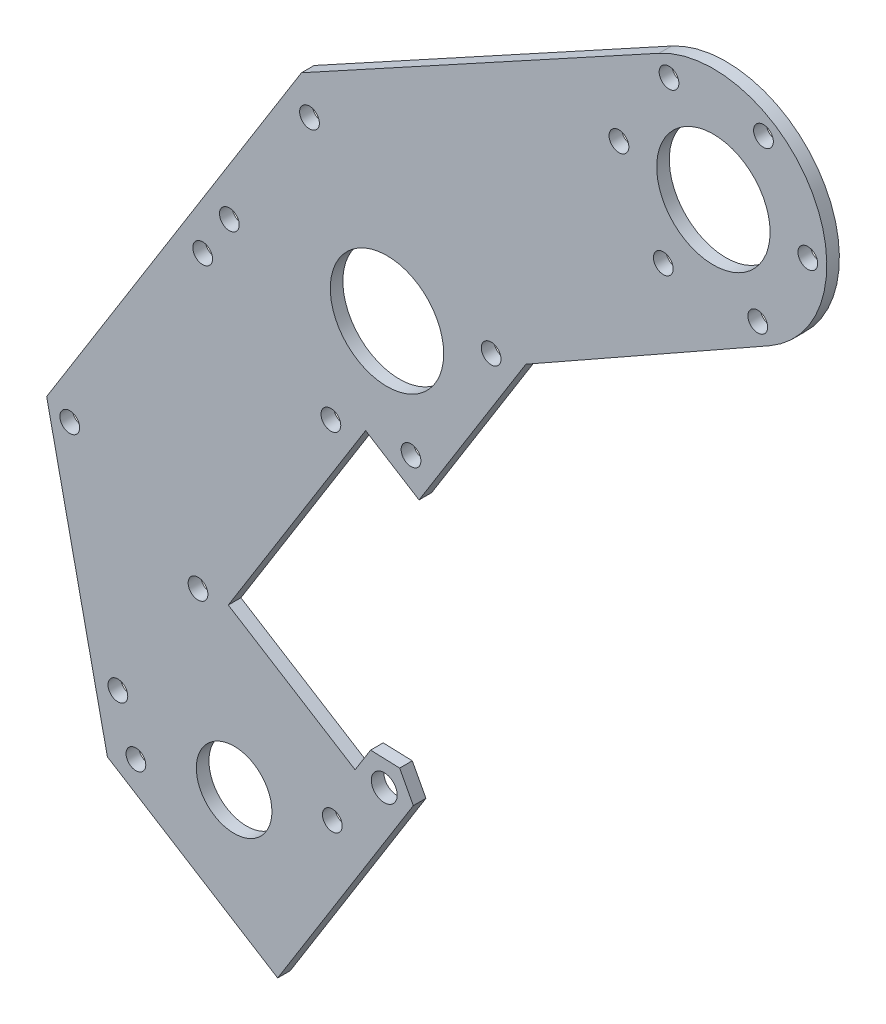
SolidWorks part; units mm, degrees
material "6061 Alloy"
ref_plane "Front Plane" through (0, 0, 0) normal (0, 0, 1) x (1, 0, 0)
ref_plane "Top Plane" through (0, 0, 0) normal (0, 1, 0) x (1, 0, 0)
ref_plane "Right Plane" through (0, 0, 0) normal (1, 0, 0) x (0, 0, -1)
sketch "Sketch1" plane through (0, 0, -14.1946) normal (0, 0, 1) x (1, 0, 0)
  line L0 (-11.4036, 461.0409) -> (18.8813, 509.5069)
  line L1 (-54.3079, 487.8505) -> (-69.6155, 558.824)
  line L2 (8.1111, 516.2368) -> (-23.8465, 536.2061)
  line L3 (18.8813, 509.5069) -> (22.7847, 515.7536)
  line L4 (-11.4036, 461.0409) -> (-54.3079, 487.8505)
  line L5 (-69.6155, 558.824) -> (-5.4017, 661.5875)
  line L6 (-23.8465, 536.2061) -> (10.7592, 591.5868)
  line L9 (12.0145, 522.4836) -> (8.1111, 516.2368)
  line L10 (51.1419, 626.2552) -> (112.462, 660.9373)
  line L11 (10.7592, 591.5868) -> (24.222, 583.1743)
  line L13 (24.222, 583.1743) -> (51.1419, 626.2552)
  line L16 (-5.4017, 661.5875) -> (84.678, 710.8773)
  line L17 (17.3996, 519.1186) -> (21.5031, 525.6857) construction
  line L18 (22.7847, 515.7536) -> (19.3423, 522.2277)
  line L19 (19.3423, 522.2277) -> (12.0145, 522.4836)
  circle A2 centre (16.1415, 618.1747) radius 14.2875
  circle A3 centre (-22.3737, 496.6228) radius 9.525
  circle A5 centre (98.3945, 685.8096) radius 14.2875
  arc A7 (112.462, 660.9373) -> (84.678, 710.8773) centre (98.3945, 685.8096) ccw
  circle A8 centre (16.1415, 618.1747) radius 127.508 construction
  circle A9 centre (15.4568, 516.0095) radius 6.35 construction
  point P12 (-22.3737, 496.6228)
  point P33 (98.3945, 685.8096)
  dimension "D1" = 120
extrude "Boss-Extrude1" add sketch "Sketch1" along normal blind 3.175
sketch "Sketch17" plane through (0, 0, -11.0196) normal (0, 0, 1) x (1, 0, 0)
  line L0 (-47.1227, 490.909) -> (-22.3737, 496.6228)
  line L1 (-22.3737, 496.6228) -> (2.3753, 502.3365)
  line L2 (16.1415, 618.1747) -> (37.6819, 604.7147) construction
  line L12 (24.222, 583.1743) -> (51.1419, 626.2552) construction
  line L13 (37.6819, 604.7147) -> (27.587, 588.5594) construction
  line L14 (27.587, 588.5594) -> (22.2019, 591.9244) construction
  line L15 (22.2019, 591.9244) -> (-28.9566, 623.8918) construction
  line L16 (-5.4017, 661.5875) -> (-69.6155, 558.824) construction
  line L17 (-28.9566, 623.8918) -> (-23.5715, 620.5268) construction
  line L18 (-23.5715, 620.5268) -> (-3.3816, 652.8374) construction
  line L19 (-3.3816, 652.8374) -> (42.3918, 624.2351) construction
  line L20 (10.7592, 591.5868) -> (5.3741, 594.9518) construction
  line L21 (5.3741, 594.9518) -> (-31.4748, 535.9811) construction
  line L22 (-31.4748, 535.9811) -> (-51.6648, 503.6705) construction
  line L23 (5.3741, 594.9518) -> (2.0091, 589.5667) construction
  line L24 (-31.4748, 535.9811) -> (-63.7855, 556.1711) construction
  line L25 (2.0091, 589.5667) -> (-30.3015, 609.7566) construction
  circle A0 centre (-22.3737, 496.6228) radius 25.4
  dimension "D1" = 50.8
hole_wizard "#10 Clearance Hole2" positions "Sketch20" profile "Sketch21" hole size "#10" standard "ANSI Inch" end condition through all
sketch "Sketch20" plane through (0, 0, -11.0196) normal (0, 0, 1) x (1, 0, 0)
  point P0 (2.3753, 502.3365)
  point P3 (-47.1227, 490.909)
  point P24 (-3.3816, 652.8374)
  point P27 (42.3918, 624.2351)
  point P30 (22.2019, 591.9244)
  point P33 (-23.5715, 620.5268)
  point P42 (-31.4748, 535.9811)
  point P45 (-63.7855, 556.1711)
  point P48 (-51.6648, 503.6705)
  point P54 (2.0091, 589.5667)
  point P57 (-30.3015, 609.7566)
sketch "Sketch21" plane through (2.3753, 502.3365, -11.0196) normal (1, 0, 0) x (0, -1, 0)
  line L0 (0, 0) -> (0, 3.175)
  line L1 (0, 3.175) -> (2.4892, 3.175)
  line L2 (2.4892, 3.175) -> (2.4892, 0)
  line L5 (2.4892, 0) -> (0, 0)
  line L11 (0, -6.35) -> (0, 107.95) construction
  dimension "Thru Hole Dia." = 4.9784
  dimension "Thru Hole Depth" = 3.175
sketch "Sketch22" plane through (0, 0, -11.0196) normal (0, 0, 1) x (1, 0, 0)
  line L0 (98.3945, 685.8096) -> (111.0132, 706.0038) construction
  line L2 (111.0132, 706.0038) -> (87.2152, 706.8348) construction
  line L3 (87.2152, 706.8348) -> (74.5965, 686.6407) construction
  line L4 (74.5965, 686.6407) -> (85.7758, 665.6155) construction
  line L5 (85.7758, 665.6155) -> (109.5738, 664.7845) construction
  line L6 (109.5738, 664.7845) -> (122.1925, 684.9786) construction
  line L7 (122.1925, 684.9786) -> (111.0132, 706.0038) construction
  circle A0 centre (98.3945, 685.8096) radius 23.8125 construction
hole_wizard "#10 Clearance Hole3" positions "Sketch23" profile "Sketch24" hole size "#10" standard "ANSI Inch" end condition through all
sketch "Sketch23" plane through (0, 0, -11.0196) normal (0, 0, 1) x (1, 0, 0)
  point P0 (111.0132, 706.0038)
  point P3 (122.1925, 684.9786)
  point P6 (109.5738, 664.7845)
  point P9 (85.7758, 665.6155)
  point P12 (74.5965, 686.6407)
  point P15 (87.2152, 706.8348)
sketch "Sketch24" plane through (111.0132, 706.0038, -11.0196) normal (1, 0, 0) x (0, -1, 0)
  line L0 (0, 0) -> (0, 3.175)
  line L1 (0, 3.175) -> (2.4892, 3.175)
  line L2 (2.4892, 3.175) -> (2.4892, 0)
  line L5 (2.4892, 0) -> (0, 0)
  line L11 (0, -6.35) -> (0, 107.95) construction
  dimension "Thru Hole Dia." = 4.9784
  dimension "Thru Hole Depth" = 3.175
hole_wizard "1/4 Clearance Hole1" positions "Sketch25" profile "Sketch26" hole size "1/4" standard "ANSI Inch" end condition through all
sketch "Sketch25" plane through (0, 0, -11.0196) normal (0, 0, 1) x (1, 0, 0)
  point P0 (15.4568, 516.0095)
sketch "Sketch26" plane through (15.4568, 516.0095, -11.0196) normal (1, 0, 0) x (0, -1, 0)
  line L0 (0, 0) -> (0, 3.175)
  line L1 (0, 3.175) -> (3.2639, 3.175)
  line L2 (3.2639, 3.175) -> (3.2639, 0)
  line L5 (3.2639, 0) -> (0, 0)
  line L11 (0, -6.35) -> (0, 107.95) construction
  dimension "Thru Hole Dia." = 6.5278
  dimension "Thru Hole Depth" = 3.175
